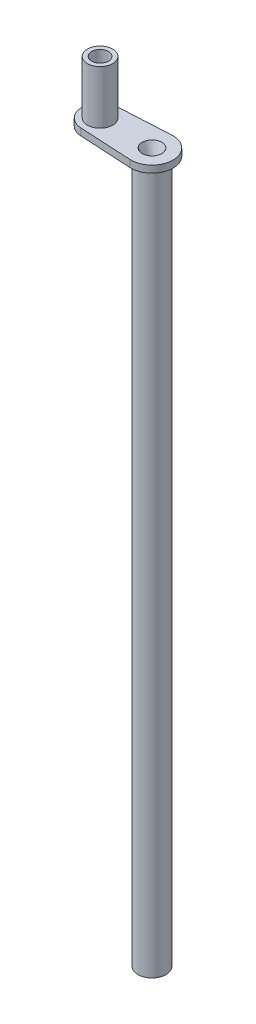
SolidWorks part; units mm, degrees
ref_plane "Alzado" through (0, 0, 0) normal (0, 0, 1) x (1, 0, 0)
ref_plane "Planta" through (0, 0, 0) normal (0, 1, 0) x (1, 0, 0)
ref_plane "Vista lateral" through (0, 0, 0) normal (1, 0, 0) x (0, 0, -1)
sketch "Croquis2" plane through (0, 0, 0) normal (0, 1, 0) x (1, 0, 0)
  circle A0 centre (-11.9753, 2.2146) radius 5
  dimension "D1" = 10
extrude "Saliente-Extruir1" add sketch "Croquis2" along normal blind 250
ref_plane "Plano1" through (0, 0, 0) normal (0, -1, 0) x (-1, 0, 0)
sketch "Croquis5" plane through (0, 0, 0) normal (0, -1, 0) x (-1, 0, 0)
  circle A0 centre (11.9753, 2.2146) radius 4
  dimension "D1" = 8
ref_plane "Plano2" through (0, 7, 0) normal (0, -1, 0) x (-1, 0, 0)
sketch "Croquis6" plane through (0, 7, 0) normal (0, -1, 0) x (-1, 0, 0)
  circle A0 centre (11.9753, 2.2146) radius 1
  dimension "D1" = 2
loft "Cortar-Recubrir1" cut profiles "Croquis6", "Croquis5" connector at (-12.7561, 7, -1.5899) connector at (-14.387, 0, 0.9766)
ref_plane "Plano3" through (0, 250, 0) normal (0, 1, 0) x (1, 0, 0)
sketch "Croquis7" plane through (0, 250, 0) normal (0, 1, 0) x (1, 0, 0)
  line L0 (-30.8266, 8.7051) -> (-12.3807, 9.7036)
  line L1 (-4.4753, 2.2146) -> (-36.9753, 2.2146) construction
  line L2 (-30.8266, -4.2759) -> (-12.3807, -5.2744)
  arc A0 (-12.3807, -5.2744) -> (-12.3807, 9.7036) centre (-11.9753, 2.2146) ccw
  arc A1 (-30.8266, 8.7051) -> (-30.8266, -4.2759) centre (-30.4753, 2.2146) ccw
  dimension "D1" = 15
  dimension "D2" = 13
  dimension "D3" = 32.5
extrude "Saliente-Extruir2" add sketch "Croquis7" along normal blind 2.5
ref_plane "Plano4" through (0, 252.5, 0) normal (0, 1, 0) x (1, 0, 0)
sketch "Croquis8" plane through (0, 252.5, 0) normal (0, 1, 0) x (1, 0, 0)
  circle A0 centre (-11.9753, 2.2146) radius 3.5
  dimension "D1" = 7
ref_plane "Plano5" through (0, 244.5, 0) normal (0, 1, 0) x (1, 0, 0)
sketch "Croquis9" plane through (0, 244.5, 0) normal (0, 1, 0) x (1, 0, 0)
  circle A0 centre (-11.9753, 2.2146) radius 1
  dimension "D1" = 2
loft "Cortar-Recubrir2" cut profiles "Croquis9", "Croquis8" connector at (-12.8787, 244.5, -2.6432) connector at (-14.6295, 252.5, 0.0668)
sketch "Croquis11" plane through (0, 252.5, 0) normal (0, 1, 0) x (1, 0, 0)
  circle A1 centre (-30.4753, 2.2146) radius 4.5
  dimension "D1" = 9
extrude "Saliente-Extruir3" add sketch "Croquis11" along normal blind 19
sketch "Croquis12" plane through (0, 271.5, 0) normal (0, 1, 0) x (1, 0, 0)
  circle A0 centre (-30.4753, 2.2146) radius 3
  dimension "D1" = 6
extrude "Cortar-Extruir1" cut sketch "Croquis12" against normal up to next contours A0
